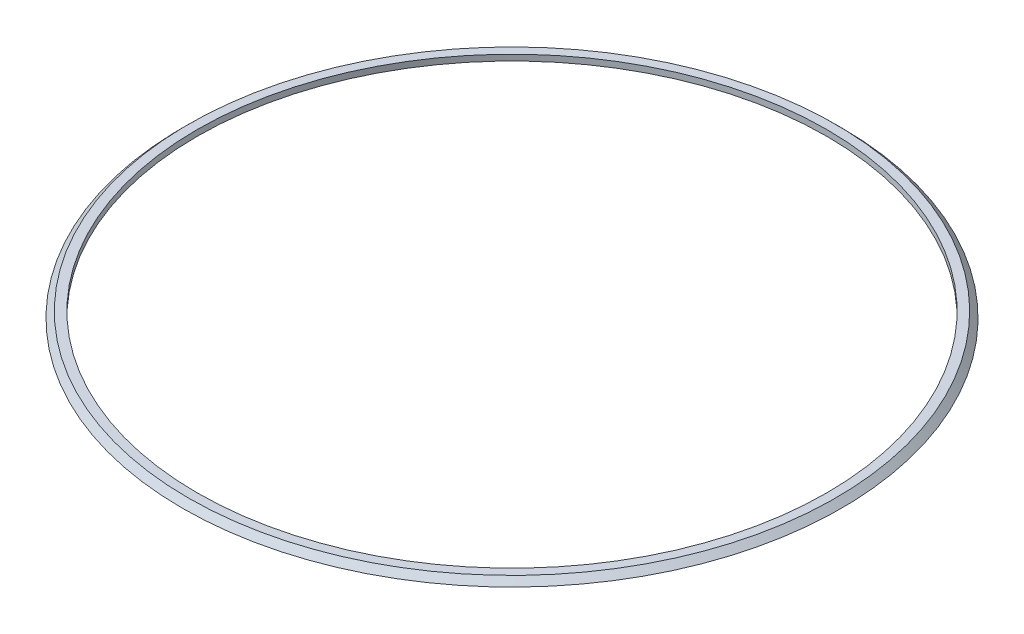
SolidWorks part; units mm, degrees
ref_plane "Front Plane" through (0, 0, 0) normal (0, 0, 1) x (1, 0, 0)
ref_plane "Top Plane" through (0, 0, 0) normal (0, 1, 0) x (1, 0, 0)
ref_plane "Right Plane" through (0, 0, 0) normal (1, 0, 0) x (0, 0, -1)
sketch "Sketch1" plane through (0, 0, 0) normal (0, 1, 0) x (1, 0, 0)
  circle A0 centre (0, 0) radius 42.5
  circle A1 centre (0, 0) radius 44.5
  dimension "D1" = 85
  dimension "D2" = 89
extrude "Boss-Extrude1" add sketch "Sketch1" along normal blind 0.8
chamfer "Chamfer1" distance 0.8 angle 45 1 edges at (0, 0.8, 44.5)
